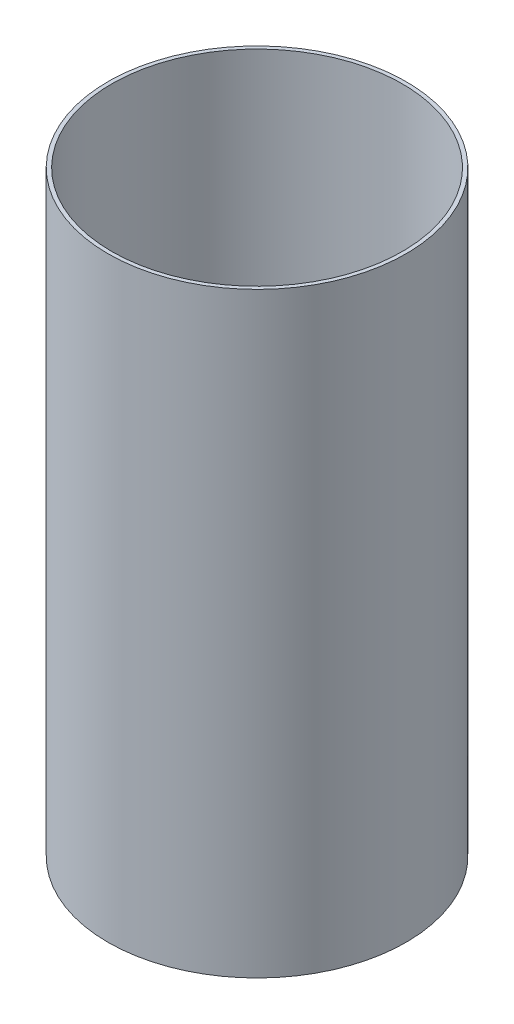
SolidWorks part; units mm, degrees
ref_plane "Front Plane" through (0, 0, 0) normal (0, 0, 1) x (1, 0, 0)
ref_plane "Top Plane" through (0, 0, 0) normal (0, 1, 0) x (1, 0, 0)
ref_plane "Right Plane" through (0, 0, 0) normal (1, 0, 0) x (0, 0, -1)
sketch "Sketch1" plane through (0, 0, 0) normal (0, 1, 0) x (1, 0, 0)
  circle A0 centre (0, 0) radius 75
  dimension "D1" = 150
extrude "Boss-Extrude1" add sketch "Sketch1" along normal blind 150 and the other way blind 150 contours A0
sketch "Sketch2" plane through (0, 150, 0) normal (0, 1, 0) x (1, 0, 0)
  circle A0 centre (0, 0) radius 73.0855
extrude "Cut-Extrude2" cut sketch "Sketch2" against normal blind 315 and the other way blind 10 contours A0
